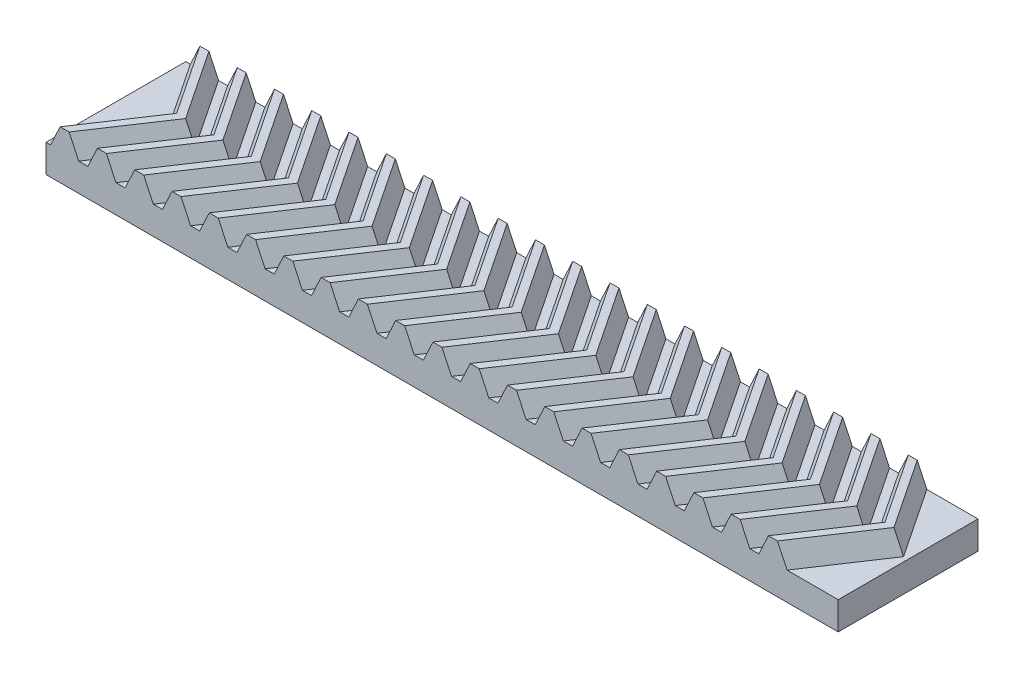
SolidWorks part; units mm, degrees
material "ABS"
ref_plane "Front Plane" through (0, 0, 0) normal (0, 0, 1) x (1, 0, 0)
ref_plane "Top Plane" through (0, 0, 0) normal (0, 1, 0) x (1, 0, 0)
ref_plane "Right Plane" through (0, 0, 0) normal (1, 0, 0) x (0, 0, -1)
sketch "Sketch1" plane through (0, 0, 0) normal (0, 0, 1) x (1, 0, 0)
  line L0 (0, -3) -> (0, 2.2) construction
  line L1 (-0.4837, 2.2) -> (0.4837, 2.2)
  line L2 (0.5337, 2.2) -> (1.5596, 0) construction
  line L4 (2, 0) -> (2, -3)
  line L5 (2, -3) -> (-2, -3)
  line L7 (0, 0.2) -> (2, 0.2) construction
  line L8 (2, 0.2) -> (2, 2.2) construction
  line L9 (2, 1.2) -> (0, 1.2) construction
  line L11 (2, 2.2) -> (0, 2.2) construction
  line L14 (0.4837, 2.2) -> (1.5096, 0)
  line L15 (2, 0) -> (1.5096, 0)
  line L16 (-2, 0) -> (-2, -3)
  line L17 (-2, 0) -> (-1.5096, 0)
  line L18 (-0.4837, 2.2) -> (-1.5096, 0)
  point P12 (1, 1.2)
  dimension "D3" = 2
  dimension "D4" = 155
  dimension "D5" = 4
  dimension "D1" = 0.2
  dimension "D2" = 3
  dimension "D6" = 0.05
sketch "Sketch2" plane through (0, 0, 0) normal (0, 1, 0) x (1, 0, 0)
  line L0 (0, 0) -> (-5, -7.5)
  dimension "D1" = 5
  dimension "D2" = 7.5
sweep "Sweep Half Tooth" add profiles "Sketch1" path "Sketch2"
sketch "Sketch3" plane through (0, 0, 0) normal (0, 0, 1) x (1, 0, 0)
  line L1 (-7, -3) -> (2, -3)
  line L2 (-7, -3) -> (-7, 0)
  line L3 (-7, 0) -> (2, 0)
  line L4 (2, -3) -> (2, 0)
extrude "Extrude End" add sketch "Sketch3" along normal up to surface (7.5 mm away) up to face at (-5, -0.2, 7.5)
pattern_linear "Pattern Half Teeth" count 20 spacing 4 along (1, 0, 0) of "Sweep Half Tooth", "Extrude End"
mirror "Mirror Teeth" about plane through (0, 0, 0) normal (0, 0, 1) of bodies 105
equation "\"nTeeth\"=20"
equation "\"xThickness\" = 15"
equation "\"aPressure\"=25"
equation "\"xWall\"=3"
equation "\"pitch\"=4"
equation "\"rHeight\"=2"
equation "\"xClearance\"=0.05"
equation "\"rClearance\"=0.2"
equation "\"D4@Sketch1\"=180-\"aPressure\""
equation "\"D5@Sketch1\"=\"pitch\""
equation "\"D6@Sketch1\"=\"xClearance\""
equation "\"D3@Sketch1\"=\"rHeight\""
equation "\"D1@Sketch1\"=\"rClearance\""
equation "\"D2@Sketch1\"=\"xWall\""
equation "\"D2@Sketch2\"=\"xThickness\"/2"
equation "\"xSkew\"= \"xThickness\" / 3"
equation "\"D1@Sketch2\"=\"xSkew\""
equation "\"D1@Pattern Half Teeth\"=\"nTeeth\""
